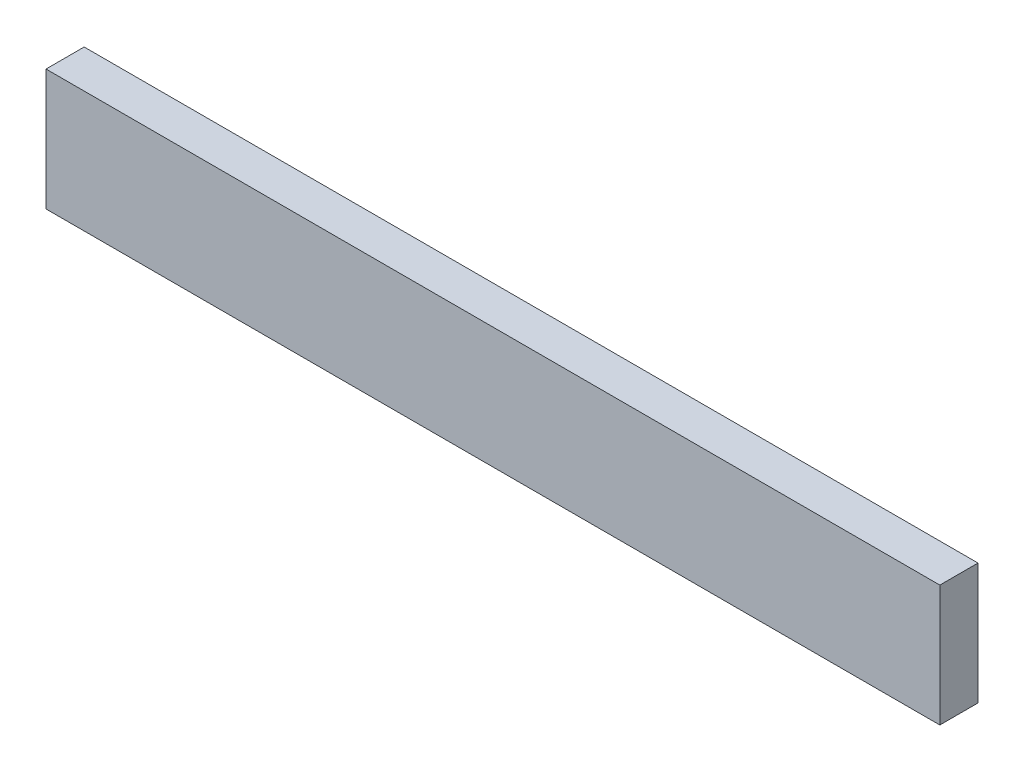
SolidWorks part; units mm, degrees
ref_plane "Front Plane" through (0, 0, 0) normal (0, 0, 1) x (1, 0, 0)
ref_plane "Top Plane" through (0, 0, 0) normal (0, 1, 0) x (1, 0, 0)
ref_plane "Right Plane" through (0, 0, 0) normal (1, 0, 0) x (0, 0, -1)
sketch "Sketch1" plane through (0, 0, 0) normal (0, 0, 1) x (1, 0, 0)
  line L1 (-18.7325, -2.54) -> (18.7325, -2.54)
  line L2 (-18.7325, -2.54) -> (-18.7325, 2.54)
  line L3 (-18.7325, 2.54) -> (18.7325, 2.54)
  line L4 (18.7325, -2.54) -> (18.7325, 2.54)
  line L5 (-18.7325, -2.54) -> (18.7325, 2.54) construction
  line L6 (-18.7325, 2.54) -> (18.7325, -2.54) construction
  point P0 (0, 0)
  dimension "D1" = 37.465
  dimension "D2" = 5.08
extrude "Boss-Extrude1" add sketch "Sketch1" along normal blind 1.6
